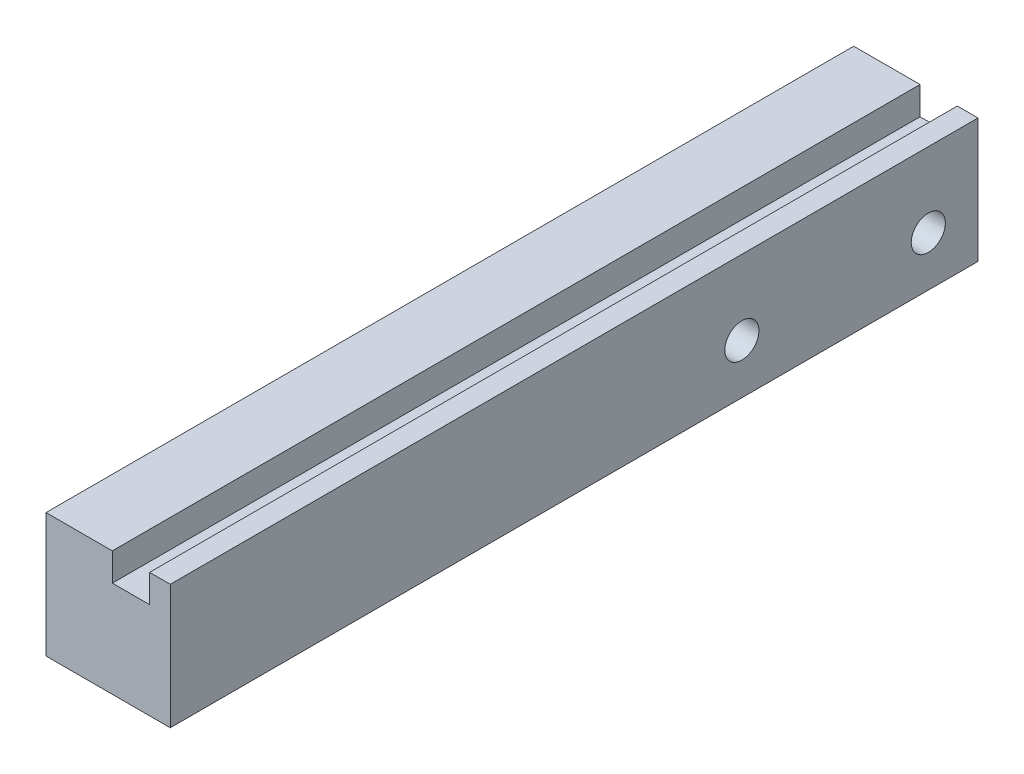
SolidWorks part; units mm, degrees
ref_plane "前视基准面" through (0, 0, 0) normal (0, 0, 1) x (1, 0, 0)
ref_plane "上视基准面" through (0, 0, 0) normal (0, 1, 0) x (1, 0, 0)
ref_plane "右视基准面" through (0, 0, 0) normal (1, 0, 0) x (0, 0, -1)
sketch "草图1" plane through (0, 0, 0) normal (0, 0, 1) x (1, 0, 0)
  line L1 (0, 0) -> (20, 0)
  line L2 (0, 0) -> (0, 20)
  line L3 (0, 20) -> (20, 20)
  line L4 (20, 0) -> (20, 20)
  dimension "D1" = 20
  dimension "D2" = 20
extrude "凸台-拉伸1" add sketch "草图1" along normal blind 130
sketch "草图2" plane through (0, 20, 0) normal (0, 1, 0) x (1, 0, 0)
  line L0 (20, 0) -> (0, 0) construction
  line L1 (10.6754, 0) -> (16.6716, 0)
  line L2 (10.6754, 0) -> (10.6754, -130)
  line L3 (10.6754, -130) -> (16.6716, -130)
  line L4 (16.6716, 0) -> (16.6716, -130)
  line L5 (20, -130) -> (0, -130) construction
extrude "切除-拉伸1" cut sketch "草图2" against normal blind 4.5
hole_wizard "M5 六角凹头螺钉的柱形沉头孔1" positions "草图3" profile "草图4" counterbore size "M5" standard "ISO" end condition through all
sketch "草图3" plane through (0, 0, 0) normal (-1, 0, 0) x (0, 0, 1)
  line L0 (130, 0) -> (0, 0) construction
  line L3 (0, 20) -> (0, 0) construction
  point P0 (8, 8)
  point P2 (38, 8)
  dimension "D1" = 30
  dimension "D2" = 8
  dimension "D3" = 8
sketch "草图4" plane through (0, 8, 8) normal (0, 1, 0) x (0, 0, 1)
  line L0 (0, 0) -> (0, 20)
  line L1 (0, 20) -> (2.75, 20)
  line L3 (2.75, 20) -> (2.75, 5.4)
  line L4 (2.75, 5.4) -> (5, 5.4)
  line L5 (5, 5.4) -> (5, 0)
  line L7 (5, 0) -> (0, 0)
  line L11 (0, -6.35) -> (0, 107.95) construction
  dimension "通孔孔直径" = 5.5
  dimension "通孔孔深度" = 20
  dimension "柱形沉头孔直径" = 10
  dimension "柱形沉头孔深度" = 5.4
